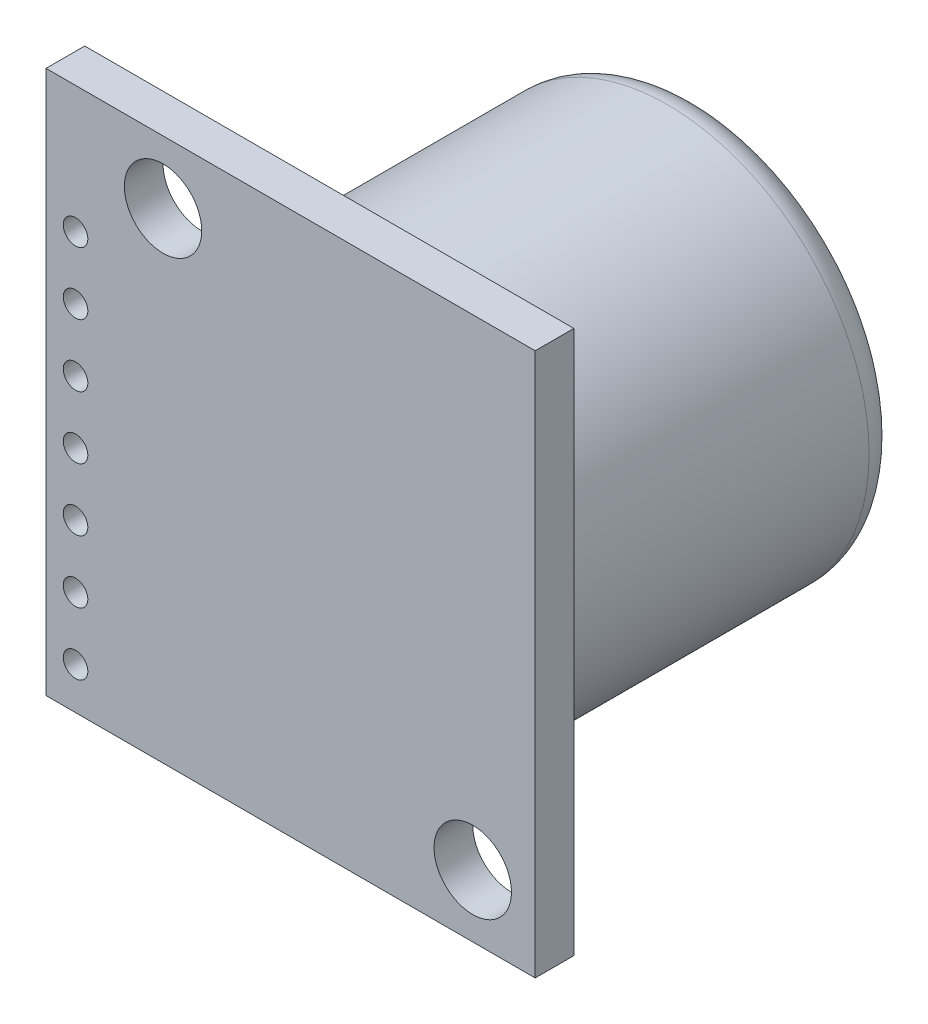
SolidWorks part; units mm, degrees
material "ABS"
ref_plane "Front Plane" through (0, 0, 0) normal (0, 0, 1) x (1, 0, 0)
ref_plane "Top Plane" through (0, 0, 0) normal (0, 1, 0) x (1, 0, 0)
ref_plane "Right Plane" through (0, 0, 0) normal (1, 0, 0) x (0, 0, -1)
sketch "Sketch1" plane through (0, 0, 0) normal (0, 0, 1) x (1, 0, 0)
  line L1 (-9.95, -11.05) -> (9.95, -11.05)
  line L2 (-9.95, -11.05) -> (-9.95, 11.05)
  line L3 (-9.95, 11.05) -> (9.95, 11.05)
  line L4 (9.95, -11.05) -> (9.95, 11.05)
  line L5 (-9.95, -11.05) -> (9.95, 11.05) construction
  line L6 (-9.95, 11.05) -> (9.95, -11.05) construction
  circle A0 centre (-5.19, 8.49) radius 1.5748
  circle A1 centre (7.41, -8.51) radius 1.5748
  circle A2 centre (-8.75, -9.35) radius 0.5
  circle A3 centre (-8.75, -6.81) radius 0.5
  circle A4 centre (-8.75, -4.27) radius 0.5
  circle A5 centre (-8.75, -1.73) radius 0.5
  circle A6 centre (-8.75, 0.81) radius 0.5
  circle A7 centre (-8.75, 3.35) radius 0.5
  circle A8 centre (-8.75, 5.89) radius 0.5
  point P0 (0, 0)
  dimension "D7" = 3.1496
  dimension "D10" = 1
  dimension "D11" = 7
  dimension "D1" = 22.1
  dimension "D2" = 19.9
  dimension "D3" = 12.6
  dimension "D4" = 17
  dimension "D5" = 2.54
  dimension "D6" = 2.54
  dimension "D8" = 1.7
  dimension "D9" = 18.7
  dimension "D12" = 0.81
extrude "Boss-Extrude1" add sketch "Sketch1" along normal blind 1.5748
sketch "Sketch2" plane through (0, 0, 0) normal (0, 0, -1) x (-1, 0, 0)
  line L0 (-7.41, -8.51) -> (5.19, 8.49) construction
  circle A0 centre (-1.11, -0.01) radius 8.2
  dimension "D1" = 16.4
extrude "Boss-Extrude2" add sketch "Sketch2" along normal blind 13.9192
fillet "Fillet2" radius 1.27 1 edges at (-7.09, -0.01, -13.9192)
